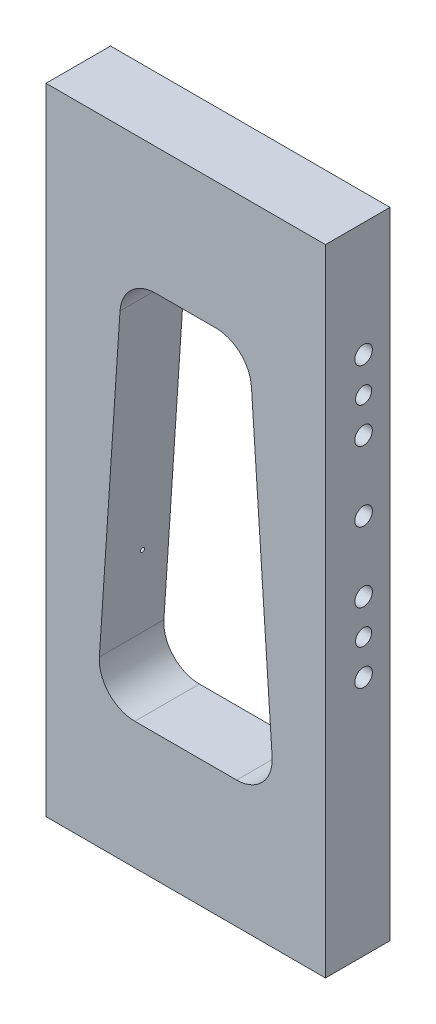
SolidWorks part; units mm, degrees
material "AISI 316 Annealed Stainless Steel Bar (SS)"
ref_plane "Front" through (0, 0, 0) normal (0, 0, 1) x (1, 0, 0)
ref_plane "Top" through (0, 0, 0) normal (0, 1, 0) x (1, 0, 0)
ref_plane "Right" through (0, 0, 0) normal (1, 0, 0) x (0, 0, -1)
sketch "Sketch1" plane through (0, 0, 0) normal (0, 0, 1) x (1, 0, 0)
  line L0 (-27.5, 0) -> (27.5, 0) construction
  line L1 (-27.5, -50) -> (27.5, -50)
  line L2 (-27.5, -50) -> (-27.5, 50)
  line L3 (-27.5, 50) -> (27.5, 50)
  line L4 (27.5, -50) -> (27.5, 50)
  dimension "D1" = 100
  dimension "D2" = 55
extrude "Boss-Extrude1" add sketch "Sketch1" along normal blind 12.7
sketch "Sketch21" plane through (0, 0, 12.7) normal (0, 0, 1) x (1, 0, 0)
  line L0 (27.5, 50) -> (-27.5, 50) construction
  line L1 (-27.5, -50) -> (27.5, -50) construction
  circle A0 centre (0, 50) radius 10.5 construction
  circle A1 centre (0, -50) radius 10.5 construction
  ellipse E0 centre (0, 50) end of major axis (14, 50) minor radius 10.5 construction
  ellipse E1 centre (0, -50) end of major axis (14, -50) minor radius 10.5
  dimension "D1" = 21
  dimension "D2" = 28
extrude "Cut-Extrude1" [suppressed] cut sketch "Sketch21" against normal through all
fillet "Fillet2" [suppressed] radius 15
fillet "Fillet1" [suppressed] radius 5 profile chamfer
hole_wizard "#8-32 Tapped Hole1" positions "Sketch15" profile "Sketch16" tap size "#8-32" standard "ANSI Inch"
sketch "Sketch15" plane through (27.5, 0, 0) normal (1, 0, 0) x (0, 0, -1)
  line L0 (-12.7, 0) -> (-5.2, 0) construction
  line L2 (-5.2, 0) -> (-5.2, 13.75) construction
  line L3 (-5.2, 13.75) -> (-5.2, 27.5) construction
  line L6 (-5.2, -27.5) -> (-5.2, -13.75) construction
  line L7 (-5.2, -13.75) -> (-5.2, 0) construction
  line L8 (-5.2, 0) -> (0, 0) construction
  line L10 (-12.7, -50) -> (-12.7, 50) construction
  line L12 (0, -50) -> (0, 50) construction
  point P0 (-5.2, -27.5)
  point P3 (-5.2, -13.75)
  point P6 (-5.2, 0)
  point P9 (-5.2, 27.5)
  point P12 (-5.2, 13.75)
  dimension "D1" = 7.5
  dimension "D2" = 13.75
sketch "Sketch16" plane through (27.5, -27.5, 5.2) normal (0, 1, 0) x (0, 0, -1)
  line L0 (0, 0) -> (0, 11.7478)
  line L1 (0, 11.7478) -> (1.7272, 10.71)
  line L2 (1.7272, 10.71) -> (1.7272, 0)
  line L5 (1.7272, 0) -> (0, 0)
  line L10 (0, 11.7478) -> (-1.7272, 10.71) construction
  line L11 (0, -6.35) -> (0, 107.95) construction
  dimension "Tap Drill Dia." = 3.4544
  dimension "Tap Drill Depth" = 10.71
  dimension "Drill Angle" = 118
cosmetic thread "Hole Thread5" parameters "D1"=8.33, "D2"=4.1656
cosmetic thread "Hole Thread6" parameters "D1"=8.33, "D2"=4.1656
cosmetic thread "Hole Thread7" parameters "D1"=8.33, "D2"=4.1656
cosmetic thread "Hole Thread8" parameters "D1"=8.33, "D2"=4.1656
cosmetic thread "Hole Thread9" parameters "D1"=8.33, "D2"=4.1656
hole_wizard "1/8 (0.1250) Dowel Hole1" positions "Sketch19" profile "Sketch20" hole size "1/8" standard "ANSI Inch"
sketch "Sketch19" plane through (27.5, 0, 0) normal (1, 0, 0) x (0, 0, -1)
  line L0 (-5.2, -27.5) -> (-5.2, -13.75) construction
  line L3 (-5.2, 13.75) -> (-5.2, 27.5) construction
  point P0 (-5.2, -20.625)
  point P2 (-5.2, 20.625)
sketch "Sketch20" plane through (27.5, -20.625, 5.2) normal (0, 1, 0) x (0, 0, -1)
  line L0 (0, 0) -> (0, 4.9539)
  line L1 (0, 4.9539) -> (1.5875, 4)
  line L2 (1.5875, 4) -> (1.5875, 0)
  line L5 (1.5875, 0) -> (0, 0)
  line L10 (0, 4.9539) -> (-1.5875, 4) construction
  line L11 (0, -6.35) -> (0, 107.95) construction
  dimension "Hole Dia." = 3.175
  dimension "Hole Depth" = 4
  dimension "Drill Angle" = 118
mirror "Mirror1" about plane through (0, 0, 0) normal (1, 0, 0) of "1/8 (0.1250) Dowel Hole1", "#8-32 Tapped Hole1"
sketch "Sketch23" plane through (0, 0, 0) normal (0, 0, -1) x (-1, 0, 0)
  line L0 (27.5, 50) -> (27.5, -50) construction
  line L1 (-27.5, -50) -> (27.5, -50)
  line L2 (-27.5, -50) -> (-27.5, -75)
  line L3 (-27.5, -75) -> (27.5, -75)
  line L4 (27.5, -50) -> (27.5, -75)
  dimension "D1" = 25
extrude "Boss-Extrude2" add sketch "Sketch23" against normal up to surface (12.7 mm away) contours L3 L4 L1 L2 up to face at (0, 0, 12.7)
sketch "Sketch22" plane through (0, 0, 0) normal (0, 0, -1) x (-1, 0, 0)
  line L0 (17.5, -50) -> (12.5, 25)
  line L2 (12.5, 25) -> (-12.5, 25)
  line L3 (-12.5, 25) -> (-17.5, -50)
  line L4 (-17.5, -50) -> (17.5, -50)
  line L5 (0, -50) -> (0, 0) construction
  line L6 (0, 0) -> (0, 25) construction
  line L7 (27.5, 50) -> (27.5, -75) construction
  line L9 (-27.5, -75) -> (27.5, -75) construction
  point P2 (0, 0)
  dimension "D1" = 25
  dimension "D2" = 10
  dimension "D3" = 25
  dimension "D4" = 25
extrude "Cut-Extrude2" cut sketch "Sketch22" against normal through all
fillet "Fillet3" radius 7 4 edges at (12.5, 25, 6.35) (-12.5, 25, 6.35) (-17.5, -50, 6.35) (17.5, -50, 6.35)
